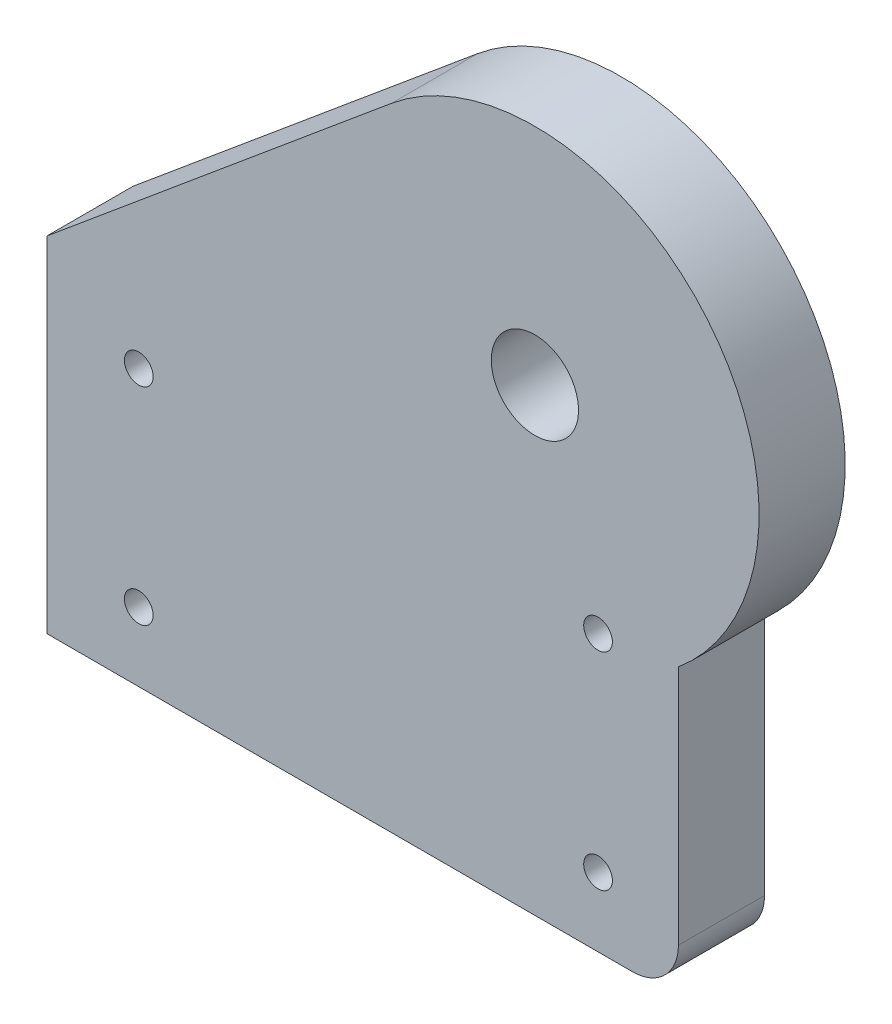
SolidWorks part; units mm, degrees
ref_plane "Front Plane" through (0, 0, 0) normal (0, 0, 1) x (1, 0, 0)
ref_plane "Top Plane" through (0, 0, 0) normal (0, 1, 0) x (1, 0, 0)
ref_plane "Right Plane" through (0, 0, 0) normal (1, 0, 0) x (0, 0, -1)
sketch "Sketch1" plane through (0, 0, 0) normal (0, 0, 1) x (1, 0, 0)
  line L0 (0, 38.1) -> (38.1, 69.85)
  line L1 (0, 0) -> (35.5012, 0)
  line L2 (0, 0) -> (0, 38.1)
  line L8 (38.1, 69.85) -> (69.85, 31.75) construction
  line L9 (35.5012, 0) -> (69.85, 0)
  line L12 (69.85, 0) -> (69.85, 31.75)
  arc A0 (38.1, 69.85) -> (69.85, 31.75) centre (53.975, 50.8) cw
  circle A2 centre (53.975, 50.8) radius 4.826
  point P0 (0, 0)
  point P1 (69.85, 44.45)
  point P10 (0, 0)
  dimension "D6" = 31.75
  dimension "D5" = 0
  dimension "D7" = 9.652
  dimension "D1" = 38.1
  dimension "D2" = 31.75
  dimension "D3" = 90
  dimension "D4" = 69.85
extrude "Boss-Extrude4" add sketch "Sketch1" along normal blind 9.525 contours L1 L2 | A0 L0 A2 region at (40.084, 33.2843, 0)
sketch "Sketch2" plane through (0, 0, 9.525) normal (0, 0, 1) x (1, 0, 0)
  line L1 (10.16, 7.62) -> (60.96, 7.62) construction
  line L2 (10.16, 7.62) -> (10.16, 30.48) construction
  line L3 (10.16, 30.48) -> (60.96, 30.48) construction
  line L4 (60.96, 7.62) -> (60.96, 30.48) construction
  line L5 (0, 0) -> (69.85, 0) construction
  line L6 (69.85, 0) -> (69.85, 31.75) construction
  circle A0 centre (10.16, 30.48) radius 1.5875
  circle A1 centre (60.96, 30.48) radius 1.5875
  circle A2 centre (60.96, 7.62) radius 1.5875
  circle A3 centre (10.16, 7.62) radius 1.5875
  dimension "D5" = 3.175
  dimension "D6" = 3.175
  dimension "D7" = 3.175
  dimension "D8" = 3.175
  dimension "D1" = 22.86
  dimension "D2" = 50.8
  dimension "D3" = 8.89
  dimension "D4" = 7.62
extrude "Cut-Extrude2" cut sketch "Sketch2" against normal up to surface (9.525 mm away) contours A0 | A3 | A1 | A2 up to face at (58.801, 50.8, 0)
fillet "Fillet1" radius 5.08 1 edges at (69.85, 0, 4.7625)
